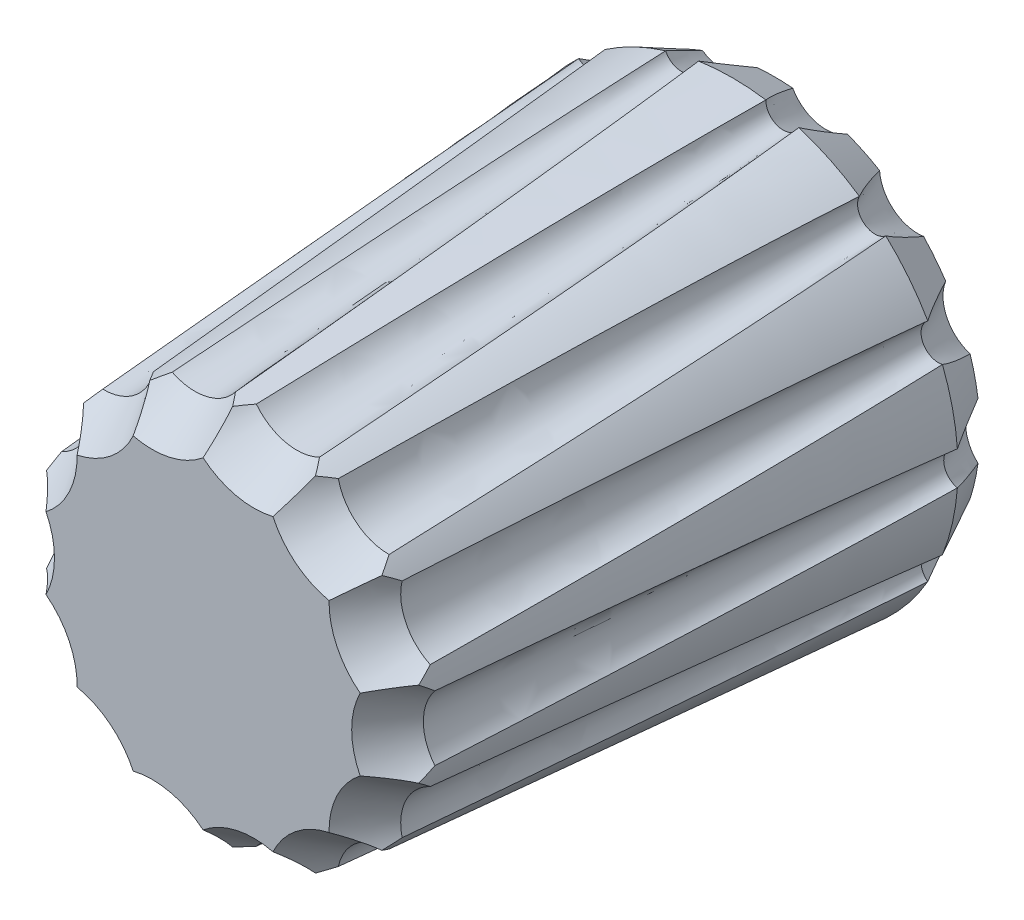
SolidWorks part; units mm, degrees
ref_plane "Plan de face" through (0, 0, 0) normal (0, 0, 1) x (1, 0, 0)
ref_plane "Plan de dessus" through (0, 0, 0) normal (0, 1, 0) x (1, 0, 0)
ref_plane "Plan de droite" through (0, 0, 0) normal (1, 0, 0) x (0, 0, -1)
sketch "Esquisse1" plane through (0, 0, 0) normal (0, 0, 1) x (1, 0, 0)
  line L0 (-13.0824, 0) -> (17.5938, 0) construction
  circle A0 centre (0, 0) radius 8
  circle A1 centre (-8, 0) radius 0.5
  circle A2 centre (-7.2078, 3.4711) radius 0.5
  circle A3 centre (-4.9879, 6.2547) radius 0.5
  circle A4 centre (-1.7802, 7.7994) radius 0.5
  circle A5 centre (1.7802, 7.7994) radius 0.5
  circle A6 centre (4.9879, 6.2547) radius 0.5
  circle A7 centre (7.2078, 3.4711) radius 0.5
  circle A8 centre (8, 0) radius 0.5
  circle A9 centre (7.2078, -3.4711) radius 0.5
  circle A10 centre (4.9879, -6.2547) radius 0.5
  circle A11 centre (1.7802, -7.7994) radius 0.5
  circle A12 centre (-1.7802, -7.7994) radius 0.5
  circle A13 centre (-4.9879, -6.2547) radius 0.5
  circle A14 centre (-7.2078, -3.4711) radius 0.5
  point P35 (0, 0)
  dimension "D1" = 16
  dimension "D2" = 1
  dimension "D3" = 14
extrude "Boss.-Extru.1" add sketch "Esquisse1" along normal blind 20 draft 4 contours A1 L0 A8 A0 A7 A6 A5 A4 A3 A2 | L0 A1 A0 A14 A13 A12 A11 A10 A9 A8 region at (0, -3.3535, 0) region at (0, 3.3535, 0)
chamfer "Chanfrein1" distance 1.5 angle 30 28 edges at (-7.7994, -1.7802, 0) (-6.7573, -3.2541, 0) (-6.2547, -4.9879, 0) (-4.6762, -5.8637, 0) (-3.4711, -7.2078, 0) (-1.6689, -7.312, 0) (0, -8, 0) (1.6689, -7.312, 0) (3.4711, -7.2078, 0) (4.6762, -5.8637, 0) (6.2547, -4.9879, 0) (6.7573, -3.2541, 0) (7.7994, -1.7802, 0) (7.5, 0, 0) (7.7994, 1.7802, 0) (6.7573, 3.2541, 0) (6.2547, 4.9879, 0) (4.6762, 5.8637, 0) (3.4711, 7.2078, 0) (1.6689, 7.312, 0) (0, 8, 0) (-1.6689, 7.312, 0) (-3.4711, 7.2078, 0) (-4.6762, 5.8637, 0) (-6.2547, 4.9879, 0) (-6.7573, 3.2541, 0) (-7.7994, 1.7802, 0) (-7.5, 0, 0) first distance on face at (-6.8905, -1.5727, 13.2305) first distance on face at (-6.1095, -2.9422, 13.2305) first distance on face at (-5.5258, -4.4067, 13.2305) first distance on face at (-4.2279, -5.3016, 13.2305) first distance on face at (-3.0666, -6.3678, 13.2305) first distance on face at (-1.5089, -6.611, 13.2305) first distance on face at (0, -7.0678, 13.2305) first distance on face at (1.5089, -6.611, 13.2305) first distance on face at (3.0666, -6.3678, 13.2305) first distance on face at (4.2279, -5.3016, 13.2305) first distance on face at (5.5258, -4.4067, 13.2305) first distance on face at (6.1095, -2.9422, 13.2305) first distance on face at (6.8905, -1.5727, 13.2305) first distance on face at (6.7811, 0, 13.2305) first distance on face at (6.8905, 1.5727, 13.2305) first distance on face at (6.1095, 2.9422, 13.2305) first distance on face at (5.5258, 4.4067, 13.2305) first distance on face at (4.2279, 5.3016, 13.2305) first distance on face at (3.0666, 6.3678, 13.2305) first distance on face at (1.5089, 6.611, 13.2305) first distance on face at (0, 7.0678, 13.2305) first distance on face at (-1.5089, 6.611, 13.2305) first distance on face at (-3.0666, 6.3678, 13.2305) first distance on face at (-4.2279, 5.3016, 13.2305) first distance on face at (-5.5258, 4.4067, 13.2305) first distance on face at (-6.1095, 2.9422, 13.2305) first distance on face at (-6.8905, 1.5727, 13.2305) first distance on face at (-6.7811, 0, 13.2305)
chamfer "Chanfrein2" distance 1.5 angle 30 28 edges at (-6.436, 1.469, 20) (-5.4972, 2.6473, 20) (-5.1612, 4.1159, 20) (-3.8042, 4.7703, 20) (-2.8643, 5.9477, 20) (-1.3577, 5.9485, 20) (0, 6.6015, 20) (1.3577, 5.9485, 20) (2.8643, 5.9477, 20) (3.8042, 4.7703, 20) (5.1612, 4.1159, 20) (5.4972, 2.6473, 20) (6.436, 1.469, 20) (6.1015, 0, 20) (6.436, -1.469, 20) (5.4972, -2.6473, 20) (5.1612, -4.1159, 20) (3.8042, -4.7703, 20) (2.8643, -5.9477, 20) (1.3577, -5.9485, 20) (0, -6.6015, 20) (-1.3577, -5.9485, 20) (-2.8643, -5.9477, 20) (-3.8042, -4.7703, 20) (-5.1612, -4.1159, 20) (-5.4972, -2.6473, 20) (-6.436, -1.469, 20) (-6.1015, 0, 20) first distance on face at (-6.865, 1.5669, 13.6046) first distance on face at (-6.0859, 2.9308, 13.6046) first distance on face at (-5.5053, 4.3904, 13.6046) first distance on face at (-4.2116, 5.2812, 13.6046) first distance on face at (-3.0552, 6.3443, 13.6046) first distance on face at (-1.5031, 6.5855, 13.6046) first distance on face at (0, 7.0416, 13.6046) first distance on face at (1.5031, 6.5855, 13.6046) first distance on face at (3.0552, 6.3443, 13.6046) first distance on face at (4.2116, 5.2812, 13.6046) first distance on face at (5.5053, 4.3904, 13.6046) first distance on face at (6.0859, 2.9308, 13.6046) first distance on face at (6.865, 1.5669, 13.6046) first distance on face at (6.7549, 0, 13.6046) first distance on face at (6.865, -1.5669, 13.6046) first distance on face at (6.0859, -2.9308, 13.6046) first distance on face at (5.5053, -4.3904, 13.6046) first distance on face at (4.2116, -5.2812, 13.6046) first distance on face at (3.0552, -6.3443, 13.6046) first distance on face at (1.5031, -6.5855, 13.6046) first distance on face at (0, -7.0416, 13.6046) first distance on face at (-1.5031, -6.5855, 13.6046) first distance on face at (-3.0552, -6.3443, 13.6046) first distance on face at (-4.2116, -5.2812, 13.6046) first distance on face at (-5.5053, -4.3904, 13.6046) first distance on face at (-6.0859, -2.9308, 13.6046) first distance on face at (-6.865, -1.5669, 13.6046) first distance on face at (-6.7549, 0, 13.6046)
sketch "Esquisse2" plane through (0, 0, 0) normal (0, 0, -1) x (-1, 0, 0)
  line L0 (1.6101, -1.1) -> (-1.6101, -1.1)
  circle A0 centre (0, 0) radius 1.95
  dimension "D1" = 3.9
  dimension "D2" = 1.1
extrude "Enlèv. mat.-Extru.1" cut sketch "Esquisse2" against normal blind 14 contours L0 A0 region at (0, 0.2776, 0)
extrude "Enlèv. mat.-Extru.2" cut sketch "Esquisse2<3>" against normal blind 0.1 contours L0 A0 region at (0, -1.4473, 0)
sketch "Esquisse2<3>" plane through (0, 0, 0) normal (0, 0, -1) x (-1, 0, 0) same geometry as "Esquisse2"
chamfer "Chanfrein3" distance 2 angle 70 1 edges at (0, -1.1, 0.1) tangent propagation no first distance on face at (0, -1.525, 0.1)
